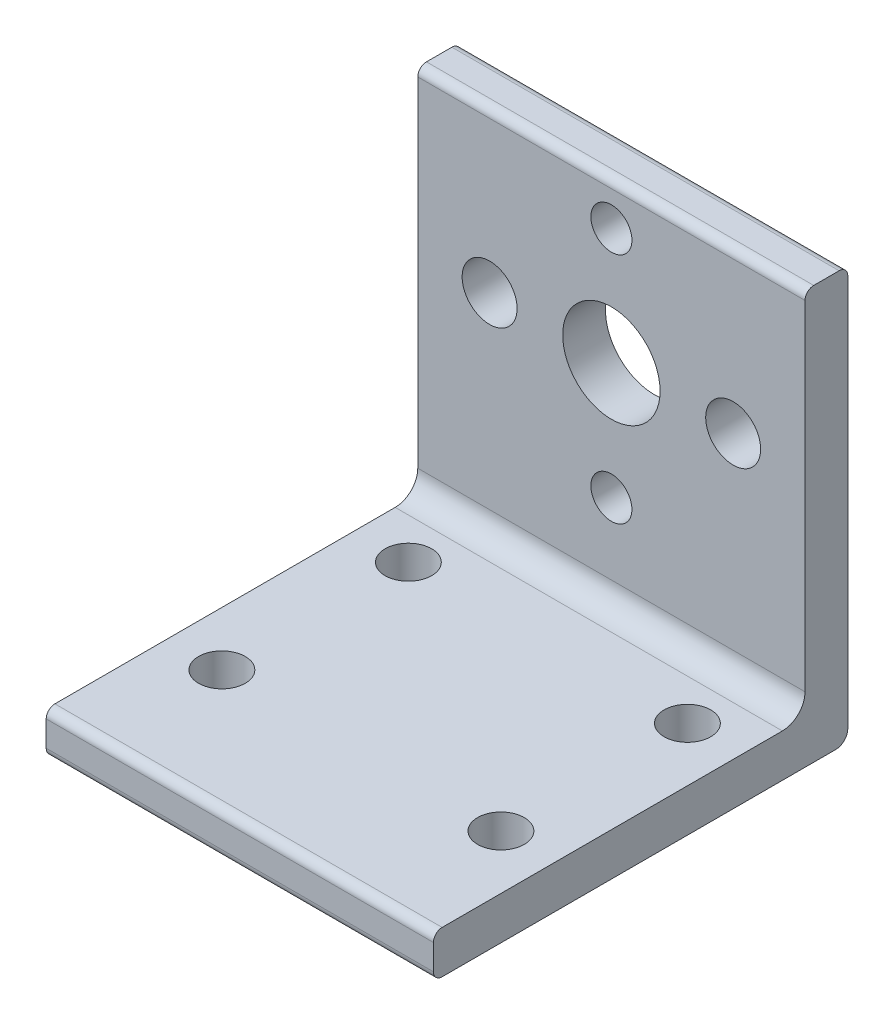
SolidWorks part; units mm, degrees
material "6061-T6 (SS)"
ref_plane "Front Plane" through (0, 0, 0) normal (0, 0, 1) x (1, 0, 0)
ref_plane "Top Plane" through (0, 0, 0) normal (0, 1, 0) x (1, 0, 0)
ref_plane "Right Plane" through (0, 0, 0) normal (1, 0, 0) x (0, 0, -1)
sketch "Sketch1" plane through (0, 0, 0) normal (1, 0, 0) x (0, 0, -1)
  line L0 (0, 0) -> (0, -30.1498)
  line L1 (0, -30.1498) -> (-30.2514, -30.1498)
  line L2 (-30.2514, -30.1498) -> (-30.2514, -27.0256)
  line L3 (-30.2514, -27.0256) -> (-3.1242, -27.0256)
  line L4 (-3.1242, -27.0256) -> (-3.1242, 0)
  line L5 (-3.1242, 0) -> (0, 0)
  dimension "D1" = 30.2514
  dimension "D2" = 30.1498
  dimension "D3" = 3.1242
  dimension "D4" = 3.1242
extrude "Boss-Extrude1" add sketch "Sketch1" along normal blind 28.2702
sketch "Sketch2" plane through (0, 0, 3.1242) normal (0, 0, 1) x (1, 0, 0)
  line L0 (14.1351, -3.1496) -> (14.1351, -20.1676) construction
  line L2 (28.2702, 0) -> (0, 0) construction
  line L3 (5.2451, -11.6586) -> (23.0251, -11.6586) construction
  line L6 (0, -11.6586) -> (28.2702, -11.6586) construction
  line L9 (0, 0) -> (0, -27.0256) construction
  line L10 (28.2702, 0) -> (28.2702, -27.0256) construction
  circle A0 centre (14.1351, -11.6586) radius 3.556
  circle A1 centre (14.1351, -3.1496) radius 1.4986
  circle A2 centre (5.2451, -11.6586) radius 2.0066
  circle A3 centre (23.0251, -11.6586) radius 2.0066
  circle A4 centre (14.1351, -20.1676) radius 1.4986
  point P0 (14.1351, -11.6586)
  dimension "D1" = 7.112
  dimension "D2" = 2.9972
  dimension "D3" = 11.6586
  dimension "D7" = 4.0132
  dimension "D4" = 17.78
  dimension "D5" = 17.018
extrude "Motor_Mount_holes" cut sketch "Sketch2" against normal through all
sketch "Sketch3" plane through (0, -27.0256, 0) normal (0, 1, 0) x (1, 0, 0)
  line L0 (14.1351, -3.1242) -> (14.1351, -30.2514) construction
  line L1 (28.2702, -3.1242) -> (0, -3.1242) construction
  line L2 (28.2702, -30.2514) -> (0, -30.2514) construction
  line L3 (28.2702, 0) -> (0, 0) construction
  line L5 (0, -14.5669) -> (28.2702, -14.5669) construction
  circle A0 centre (24.3205, -7.7597) radius 1.7018
  circle A1 centre (3.9497, -7.7597) radius 1.7018
  circle A2 centre (3.9497, -21.3741) radius 1.7018
  circle A3 centre (24.3205, -21.3741) radius 1.7018
  dimension "D1" = 3.4036
  dimension "D2" = 20.3708
  dimension "D3" = 13.6144
  dimension "D4" = 7.7597
extrude "Plate_Mount_Holes" cut sketch "Sketch3" against normal through all
fillet "Fillet1" radius 1.651 1 edges at (14.1351, -27.0256, 3.1242)
fillet "Fillet2" radius 0.889 1 edges at (14.1351, -30.1498, 0)
fillet "Fillet3" radius 0.635 4 edges at (14.1351, -30.1498, 30.2514) (14.1351, -27.0256, 30.2514) (14.1351, 0, 0) (14.1351, 0, 3.1242)
